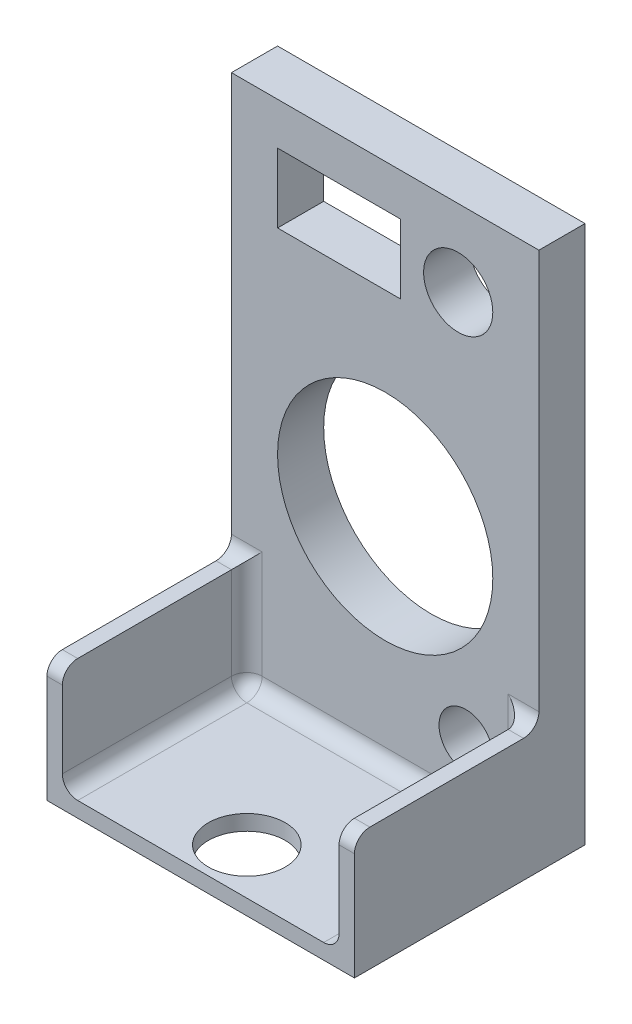
SolidWorks part; units mm, degrees
material "ABS"
ref_plane "Front Plane" through (0, 0, 0) normal (0, 0, 1) x (1, 0, 0)
ref_plane "Top Plane" through (0, 0, 0) normal (0, 1, 0) x (1, 0, 0)
ref_plane "Right Plane" through (0, 0, 0) normal (1, 0, 0) x (0, 0, -1)
sketch "Sketch1" plane through (0, 0, 0) normal (0, 0, 1) x (1, 0, 0)
  line L0 (11, 52.25) -> (3, 47.75) construction
  line L1 (3, 52.25) -> (11, 52.25)
  line L2 (3, 52.25) -> (3, 47.75)
  line L3 (3, 47.75) -> (11, 47.75)
  line L4 (11, 52.25) -> (11, 47.75)
  line L5 (0, 35) -> (20, 35) construction
  line L6 (0, 20) -> (20, 20)
  line L7 (20, 20) -> (20, 0) construction
  line L8 (0, 55) -> (20, 55)
  line L9 (0, 55) -> (0, 0)
  line L10 (0, 0) -> (20, 0)
  line L11 (20, 55) -> (20, 0)
  line L12 (20, 20) -> (0, 0) construction
  line L13 (10, 55) -> (10, 0) construction
  line L14 (17, 42) -> (3, 42)
  line L15 (17, 42) -> (17, 28)
  line L16 (17, 28) -> (3, 28)
  line L17 (3, 42) -> (3, 28)
  line L18 (10, 10) -> (0, 10) construction
  line L19 (7.5, 1) -> (12.5, 1)
  line L20 (7.5, 1) -> (7.5, 3.85)
  line L21 (7.5, 3.85) -> (12.5, 3.85)
  line L22 (12.5, 1) -> (12.5, 3.85)
  line L23 (7.5, 19) -> (7.5, 16.15)
  line L24 (7.5, 19) -> (12.5, 19)
  line L25 (12.5, 19) -> (12.5, 16.15) construction
  line L26 (7.5, 16.15) -> (12.5, 16.15)
  line L27 (14.75, 50) -> (7, 50) construction
  line L28 (1, 21) -> (1, 1)
  line L29 (1, 54) -> (19, 54)
  line L30 (1, 54) -> (1, 21)
  line L31 (1, 21) -> (19, 21)
  line L32 (19, 54) -> (19, 21)
  line L33 (1, 1) -> (19, 1)
  line L34 (19, 1) -> (19, 21)
  line L35 (1, 20) -> (19, 20)
  line L36 (0, 28) -> (1, 28)
  line L37 (19, 28) -> (20, 28)
  circle A0 centre (15.25, 25) radius 1.75
  circle A1 centre (14.75, 50) radius 2.25
  circle A2 centre (10, 10) radius 2.5
  circle A3 centre (10, 35) radius 7
  circle A4 centre (14.75, 50) radius 1.5
  circle A5 centre (7, 50) radius 1.5
  circle A6 centre (15.25, 25) radius 1.5
  point P9 (7, 50)
  point P12 (14.75, 52.25)
  point P15 (14.75, 47.75)
  point P17 (17, 50)
  point P20 (17, 25)
  point P21 (15.25, 23.25)
  point P31 (17, 35)
  point P32 (10, 28)
  dimension "D1" = 3.5
  dimension "D4" = 4.5
  dimension "D6" = 15
  dimension "D14" = 5
  dimension "D26" = 3
  dimension "D2" = 4.5
  dimension "D3" = 8
  dimension "D5" = 3
  dimension "D7" = 20
  dimension "D8" = 1
  dimension "D9" = 3
  dimension "D10" = 55
  dimension "D11" = 3
  dimension "D12" = 10
  dimension "D13" = 20
  dimension "D15" = 14
  dimension "D16" = 14
  dimension "D17" = 35
  dimension "D18" = 7.5
  dimension "D19" = 1
  dimension "D20" = 2.85
  dimension "D21" = 5
  dimension "D22" = 1
  dimension "D23" = 1
  dimension "D24" = 1
  dimension "D25" = 1
  dimension "D27" = 8
extrude "Boss-Extrude1" [suppressed] add sketch "Sketch1" along normal blind 3 contours L32 L29 L30 L31 A1 A0 L17 L14 L15 L16 L1 L4 L3 L2 | L4 L1 L2 L3 A5 | A1 A4 | A3 L16 L15 | A3 L15 L14 | A3 L14 L17 | A3 L17 L16
extrude "Boss-Extrude2" add sketch "Sketch1<7>" against normal blind 3 contours L32 L29 L30 L31 A1 A0 L17 L14 L15 L16 L1 L4 L3 L2 | L36 L9 L6 L28 L30 | L6 L34 L31 L28 | L37 L32 L34 L6 L11 | L32 L37 L11 L8 L9 L36 L30 L29 | A3 L17 L16 | A3 L14 L17 | A3 L15 L14 | A3 L16 L15 region at (0.5, 24, 0) region at (10, 20.5, 0) region at (0.336, 41.5, 0) region at (19.5, 24, 0) region at (1.3759, 24.5, 0) region at (15.4364, 40.4364, 0) region at (4.5636, 40.4364, 0) region at (15.4364, 29.5636, 0) region at (4.5636, 29.5636, 0)
sketch "Sketch1<7>" plane through (0, 0, 0) normal (0, 0, 1) x (1, 0, 0) same geometry as "Sketch1"
extrude "Boss-Extrude3" add sketch "Sketch1<8>" along normal blind 12 contours L37 L32 L34 L6 L11 | L6 L34 L31 L28 | L36 L9 L6 L28 L30 region at (0.5, 24, 0) region at (10, 20.5, 0) region at (19.5, 24, 0)
sketch "Sketch1<8>" plane through (0, 0, 0) normal (0, 0, 1) x (1, 0, 0) same geometry as "Sketch1"
sketch "Sketch2" plane through (0, 20, 0) normal (0, -1, 0) x (1, 0, 0)
  line L0 (10, 12) -> (10, 9) construction
  line L1 (0, 12) -> (20, 12) construction
  circle A0 centre (10, 9) radius 2.5
  dimension "D2" = 5
  dimension "D1" = 3
extrude "Cut-Extrude1" cut sketch "Sketch2" against normal through all
fillet "Fillet1" radius 1 9 edges at (19.5, 28, 12) (0.5, 28, 12) (1, 24.5, 0) (19, 24.5, 0) (19, 21, 6) (10, 21, 0) (1, 21, 6)
